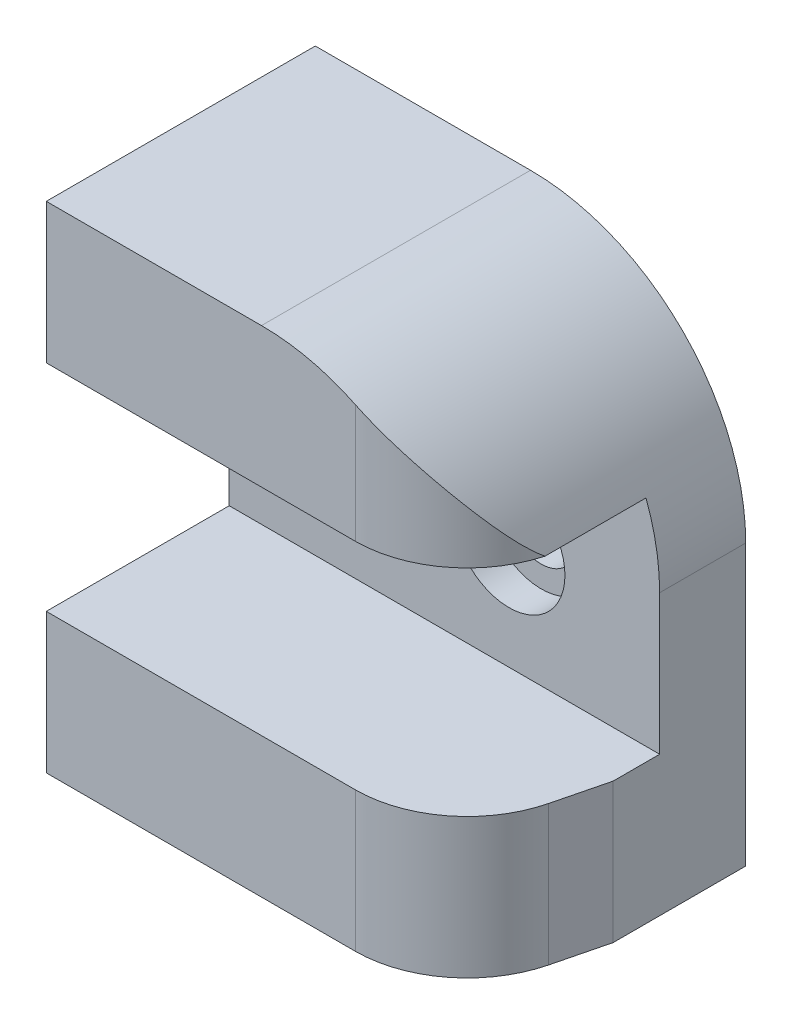
SolidWorks part; units mm, degrees
ref_plane "前视基准面" through (0, 0, 0) normal (0, 0, 1) x (1, 0, 0)
ref_plane "上视基准面" through (0, 0, 0) normal (0, 1, 0) x (1, 0, 0)
ref_plane "右视基准面" through (0, 0, 0) normal (1, 0, 0) x (0, 0, -1)
sketch "草图1" plane through (0, 0, 0) normal (0, 0, 1) x (1, 0, 0)
  line L0 (130, 95) -> (130, -95) construction
  line L1 (130, 82) -> (110, 82)
  line L2 (130, 82) -> (130, 95)
  line L3 (120, 105) -> (110, 105)
  line L4 (110, 82) -> (110, 105)
  line L5 (75, 105) -> (120, 105) construction
  line L6 (130, 105) -> (120, 105) construction
  line L7 (130, 95) -> (130, 105) construction
  arc A0 (130, 95) -> (120, 105) centre (120, 95) ccw construction
  arc A1 (130, 95) -> (120, 105) centre (120, 95) ccw
  dimension "D1" = 20
  dimension "D2" = 23
extrude "凸台-拉伸1" add sketch "草图1" along normal blind 12.5
sketch "草图2" plane through (0, 105, 0) normal (0, 1, 0) x (1, 0, 0)
  line L6 (129.4025, -8.558) -> (130, -6.1617)
  line L8 (130, -6.1617) -> (130, -12.5)
  line L9 (130, -12.5) -> (130, 0) construction
  line L10 (130, -12.5) -> (124.357, -12.5)
  arc A1 (124.357, -12.5) -> (129.4025, -8.558) centre (124.357, -7.3) ccw
  point P5 (129.9935, -6.1879)
  point P9 (129.9995, -6.1637)
extrude "切除-拉伸1" cut sketch "草图2" against normal blind 26.5
sketch "草图3" plane through (0, 0, 12.5) normal (0, 0, 1) x (1, 0, 0)
  line L0 (110, 93.5) -> (130, 93.5) construction
  line L1 (110, 105) -> (110, 82) construction
  line L4 (110, 98.5) -> (130, 98.5)
  line L5 (110, 98.5) -> (110, 88.5)
  line L6 (110, 88.5) -> (130, 88.5)
  line L7 (130, 98.5) -> (130, 88.5)
  line L8 (110, 98.5) -> (130, 88.5) construction
  line L9 (110, 88.5) -> (130, 98.5) construction
  point P4 (129.9732, 93.5)
  point P5 (110, 93.5)
  point P6 (120, 93.5)
  dimension "D1" = 10
  dimension "D2" = 20
extrude "切除-拉伸2" cut sketch "草图3" against normal blind 8.5
sketch "草图4" plane through (0, 0, 4) normal (0, 0, 1) x (1, 0, 0)
  line L0 (110, 93.5) -> (130, 93.5) construction
  line L1 (110, 98.5) -> (110, 88.5) construction
  line L3 (130, 88.5) -> (130, 95) construction
  circle A0 centre (115, 93.5) radius 1.5
  circle A2 centre (123, 93.5) radius 1.5
  point P4 (128.9724, 93.5)
  point P5 (130, 93.5)
  dimension "D1" = 3
  dimension "D2" = 8
  dimension "D3" = 5
hole_wizard "M3 六角头螺栓的柱形沉头孔1" positions "草图7" profile "草图8" counterbore size "M3" standard "GB" end condition through all
sketch "草图7" plane through (0, 0, 4) normal (0, 0, 1) x (1, 0, 0)
  point P0 (115, 93.5)
  point P3 (123, 93.5)
sketch "草图8" plane through (115, 93.5, 4) normal (1, 0, 0) x (0, -1, 0)
  line L0 (0, 0) -> (0, 4)
  line L1 (0, 4) -> (1.6, 4)
  line L3 (1.6, 4) -> (1.6, 1.5)
  line L4 (1.6, 1.5) -> (2.6, 1.5)
  line L5 (2.6, 1.5) -> (2.6, 0)
  line L7 (2.6, 0) -> (0, 0)
  line L11 (0, -6.35) -> (0, 107.95) construction
  dimension "通孔孔直径" = 3.2
  dimension "通孔孔深度" = 4
  dimension "柱形沉头孔直径" = 5.2
  dimension "柱形沉头孔深度" = 1.5
move or copy body "实体-移动/复制1" [suppressed] bodies to move or copy 109
